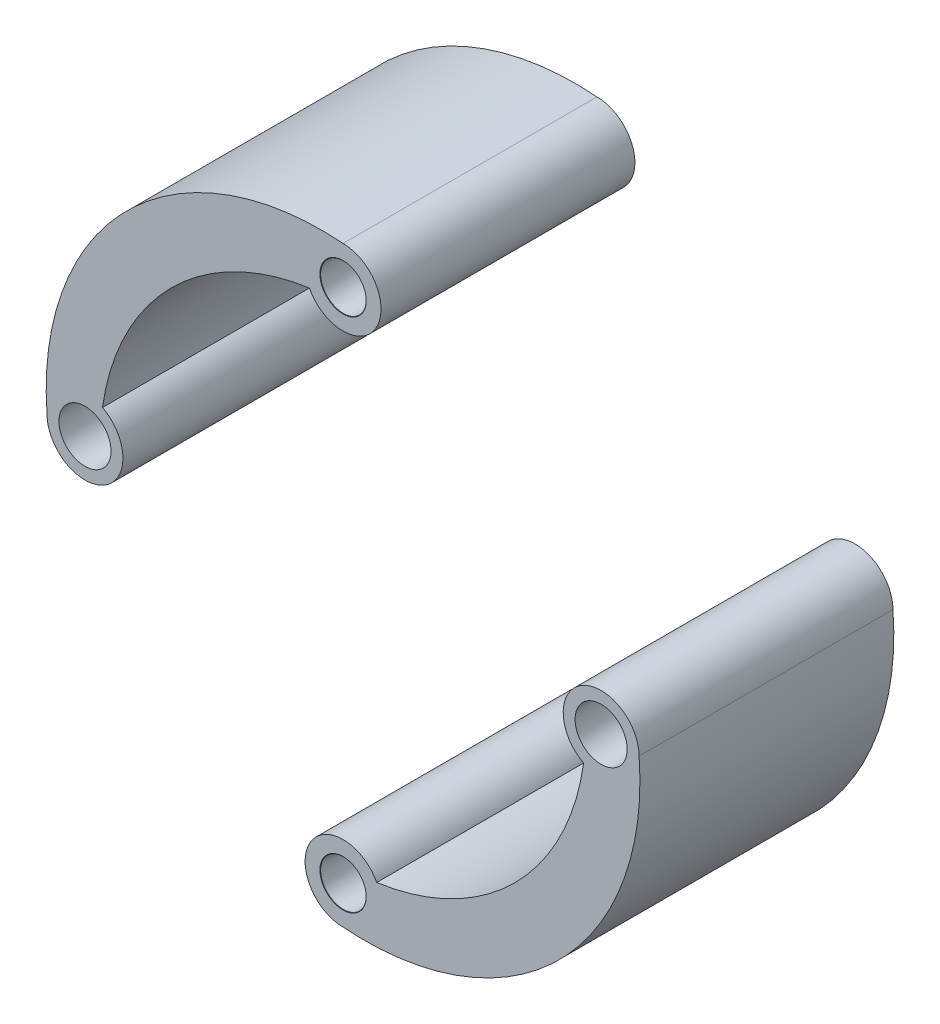
SolidWorks part; units mm, degrees
ref_plane "Front Plane" through (0, 0, 0) normal (1, 0, 0) x (0, 1, 0)
ref_plane "Top Plane" through (0, 0, 0) normal (0, 0, 1) x (0, 1, 0)
ref_plane "Right Plane" through (0, 0, 0) normal (0, 1, 0) x (-1, 0, 0)
sketch "Sketch1" plane through (0, 0, 0) normal (0, 0, 1) x (0, 1, 0)
  line L0 (0, -17) -> (0, 17) construction
  line L1 (-17, 0) -> (17, 0) construction
  line L2 (0, 0) -> (1.4142, 1.4142) construction
  line L3 (0, 0) -> (-1.4142, -1.4142) construction
  circle A0 centre (0, 17) radius 2.5
  circle A1 centre (0, -17) radius 2.5
  circle A2 centre (-17, 0) radius 2.5
  circle A3 centre (17, 0) radius 2.5
  arc A4 (0, 19.5) -> (19.5, 0) centre (1.4142, 1.4142) cw
  arc A5 (2.2175, 15.8456) -> (15.8456, 2.2175) centre (0, 0) cw
  arc A6 (-19.5, 0) -> (0, -19.5) centre (-1.4142, -1.4142) ccw
  arc A7 (-2.2175, -15.8456) -> (-15.8456, -2.2175) centre (0, 0) cw
  circle A8 centre (0, 0) radius 13.75 construction
  point P4 (0, 0)
  point P8 (0, 0)
  dimension "D3" = 5
  dimension "D4" = 5
  dimension "D5" = 16
  dimension "D6" = 45
  dimension "D7" = 16
  dimension "D8" = 2
  dimension "D9" = 27.5
  dimension "D1" = 34
  dimension "D2" = 34
  dimension "D10" = 2
extrude "Boss-Extrude1" add sketch "Sketch1" along normal blind 16.7224 contours A0 | A0 A5 A3 | A3 | A2 | A1 | A1 A7 A2 region at (-17, 0, 0) region at (-11.8979, 11.8979, 0) region at (0, 17, 0) region at (17, 0, 0) region at (11.8979, -11.8979, 0) region at (0, -17, 0)
hole_wizard "Ø3.0mm Dowel Hole1" positions "Sketch3" profile "Sketch5" hole size "Ø3.0" standard "ANSI Metric" end condition through all
sketch "Sketch3" plane through (0, 0, 16.7224) normal (0, 0, 1) x (1, 0, 0)
  point P0 (0, 17)
  point P3 (0, -17)
sketch "Sketch5" plane through (0, 17, 16.7224) normal (1, 0, 0) x (0, -1, 0)
  line L0 (0, 0) -> (0, 16.7224)
  line L1 (0, 16.7224) -> (1.5, 16.7224)
  line L2 (1.5, 16.7224) -> (1.5, 0.021)
  line L3 (1.5, 0.021) -> (1.525, 0)
  line L5 (1.525, 0) -> (0, 0)
  line L6 (-1.5, 0.021) -> (-1.525, 0) construction
  line L11 (0, -6.35) -> (0, 107.95) construction
  dimension "Thru Hole Dia." = 3
  dimension "Thru Hole Depth" = 16.7224
  dimension "Near C'Sink Dia." = 3.05
  dimension "Near C'Sink Angle" = 100
sketch "Sketch6" plane through (0, 0, 16.7224) normal (0, 0, 1) x (1, 0, 0)
  circle A0 centre (-17, 0) radius 1.715
  circle A1 centre (17, 0) radius 1.715
  dimension "D1" = 3.43
extrude "Cut-Extrude1" cut sketch "Sketch6" against normal blind 5
sketch "Sketch7" plane through (0, 0, 0) normal (0, 0, -1) x (1, 0, 0)
  circle A0 centre (-17, 0) radius 1.715
  circle A1 centre (17, 0) radius 1.715
  dimension "D1" = 3.43
extrude "Cut-Extrude2" cut sketch "Sketch7" against normal blind 5
equation "\"Alum Bracket Thickness\"= 0.35in"
equation "\"D1@Boss-Extrude1\"=28-\"Alum Bracket Thickness\"-\"spur gear gap\""
equation "\"spur gear gap\" = 0.094in"
